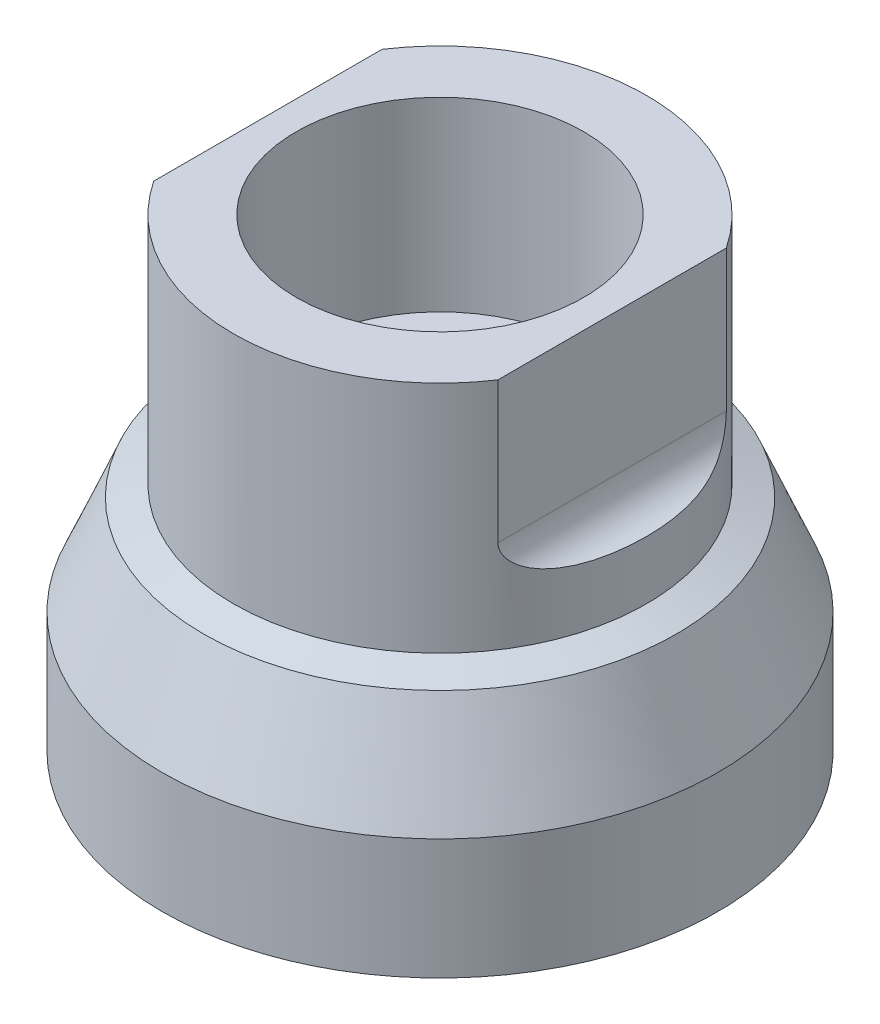
SolidWorks part; units mm, degrees
ref_plane "Front Plane" through (0, 0, 0) normal (0, 0, 1) x (1, 0, 0)
ref_plane "Top Plane" through (0, 0, 0) normal (0, 1, 0) x (1, 0, 0)
ref_plane "Right Plane" through (0, 0, 0) normal (1, 0, 0) x (0, 0, -1)
sketch "Sketch1" plane through (0, 0, 0) normal (1, 0, 0) x (0, 0, -1)
  line L0 (0, 0) -> (0, 17.2593) construction
  line L1 (0, 17.2593) -> (-15.24, 17.2593)
  line L2 (-15.24, 17.2593) -> (-15.24, 0)
  line L3 (-15.24, 0) -> (0, 0) construction
  line L4 (-15.24, 0) -> (-17.4625, -0.8089)
  line L5 (-17.4625, -0.8089) -> (-20.5105, -8.1407)
  line L6 (-20.5105, -17.0307) -> (-8.7845, -20.8407)
  line L7 (-8.7845, -20.8407) -> (0, -20.8407)
  line L8 (0, -20.8407) -> (0, 0) construction
  line L9 (-13.0457, 17.2593) -> (-13.0457, 0) construction
  line L10 (0, 17.2593) -> (0, -20.8407) construction
  line L11 (-20.5105, -8.1407) -> (-20.5105, -17.0307)
  line L12 (0, 17.2593) -> (0, -20.8407)
  dimension "D1" = 17.2593
  dimension "D2" = 38.1
  dimension "D3" = 110
  dimension "D4" = 41.021
  dimension "D5" = 38.1
  dimension "D6" = 30.48
  dimension "D7" = 25.4
  dimension "D8" = 34.29
  dimension "D9" = 18
  dimension "D10" = 34.925
revolve "Revolve1" add sketch "Sketch1" angle 360 mid plane about L12
sketch "Sketch3" plane through (0, 0, 0) normal (0, 0, 1) x (1, 0, 0)
  line L0 (-20.5105, -17.0307) -> (-8.7845, -20.8407) construction
  line L1 (-20.5105, -17.0307) -> (-5.161, -22.0181)
  line L2 (-12.8358, -19.5244) -> (-8.8848, -7.3647) construction
  point P7 (-8.7845, -20.8407)
  dimension "D1" = 3.81
ref_plane "Plane1" through (-5.872, 1.9079, 0) normal (0.9511, -0.309, 0) x (0, 0, -1)
sketch "Sketch4" plane through (-5.872, 1.9079, 0) normal (0.9511, -0.309, 0) x (0, 0, -1)
  line L0 (0, -25.0753) -> (0, -4.7553) construction
  line L1 (0, -7.7423) -> (0, -0.7693) construction
  line L2 (0, -4.7553) -> (-6.8326, -8.3882)
  line L3 (-6.8326, -8.3882) -> (-6.8326, -25.0753)
  line L4 (-6.8326, -25.0753) -> (0, -25.0753)
  line L5 (0, -25.0753) -> (0, -4.7553)
  dimension "D1" = 2.54
  dimension "D2" = 20.32
  dimension "D3" = 13.6652
  dimension "D4" = 118
revolve "Cut-Revolve2" cut sketch "Sketch4" angle 360 mid plane about L0
ref_plane "Plane2" through (-6.9638, -21.4323, 0) normal (-0.309, -0.9511, 0) x (0.9511, -0.309, 0)
ref_plane "Plane3" through (-7.3998, -22.7743, 0) normal (-0.309, -0.9511, 0) x (0.9511, -0.309, 0)
sketch "Sketch5" plane through (-7.3998, -22.7743, 0) normal (-0.309, -0.9511, 0) x (0.9511, -0.309, 0)
  circle A0 centre (-6.1742, 0) radius 6.858
  dimension "Outlet OD" = 13.716
curve "Helix/Spiral1"
sketch "Sketch8" plane through (0, 0, 0) normal (0, 0, 1) x (1, 0, 0)
  line L0 (0, -20.8407) -> (8.7845, -20.8407)
  line L1 (0, -17.0307) -> (0, -20.8407) construction
  line L2 (-7.6682, -20.8407) -> (8.7845, -20.8407) construction
  line L3 (8.7845, -20.8407) -> (20.5105, -17.0307) construction
  line L4 (8.7845, -20.8407) -> (20.5105, -17.0307)
  line L5 (20.5105, -17.0307) -> (20.5105, -33.1701)
  line L6 (20.5105, -33.1701) -> (0, -33.1701)
  line L7 (0, -33.1701) -> (0, -20.8407)
sketch "Sketch6" plane through (0, 0, 0) normal (0, 0, 1) x (1, 0, 0)
  line L0 (-12.8358, -19.5244) -> (-8.8848, -7.3647) construction
  line L4 (-6.2544, -21.7092) -> (-7.6347, -22.0025) construction
  line L5 (-7.6347, -22.0025) -> (-6.6904, -23.0512) construction
  line L6 (-6.6904, -23.0512) -> (-6.2544, -21.7092) construction
  line L7 (-7.4621, -21.9659) -> (-7.5166, -22.1336) construction
  line L8 (-6.4269, -21.7458) -> (-6.8085, -22.9201) construction
  line L9 (-7.6347, -22.0025) -> (-7.4894, -22.0497) construction
  line L10 (-6.6177, -22.333) -> (-6.4724, -22.3802) construction
  line L11 (-6.5451, -22.3566) -> (-6.7495, -22.9857) construction
  line L13 (-6.3407, -21.7275) -> (-7.4621, -21.9659)
  line L14 (-7.4621, -21.9659) -> (-7.5166, -22.1336)
  line L15 (-7.5166, -22.1336) -> (-6.6904, -23.0512)
  line L16 (-7.6347, -22.0025) -> (-8.6147, -21.6841) construction
  line L17 (-6.6904, -23.0512) -> (-6.5227, -23.1057) construction
  line L18 (-6.5227, -23.1057) -> (-6.4682, -22.938) construction
  line L19 (-6.4682, -22.938) -> (-6.4137, -22.7702) construction
  line L20 (-6.4137, -22.7702) -> (-6.3592, -22.6024) construction
  line L21 (-6.3592, -22.6024) -> (-6.3047, -22.4347) construction
  line L22 (-6.3047, -22.4347) -> (-6.2502, -22.2669) construction
  line L23 (-6.2502, -22.2669) -> (-6.1956, -22.0992) construction
  line L24 (-6.1956, -22.0992) -> (-6.1411, -21.9314) construction
  line L25 (-6.1411, -21.9314) -> (-6.0866, -21.7637) construction
  line L26 (-6.0866, -21.7637) -> (-6.2544, -21.7092) construction
  line L27 (-6.5451, -22.3566) -> (-6.3407, -21.7275) construction
  line L28 (-6.3407, -21.7275) -> (-6.6904, -23.0512)
  point P18 (-6.5099, -22.368)
  dimension "D1" = 1.4111
sweep "Sweep1" [suppressed] add profiles "Sketch6" path "Helix/Spiral1"
sketch "Sketch10" plane through (0, 0, 0) normal (0, 0, 1) x (1, 0, 0)
  line L0 (-12.8358, -19.5244) -> (-20.5105, -17.0307) construction
  line L1 (-20.5105, -17.0307) -> (-16.6639, -15.0708)
  line L2 (-16.6639, -15.0708) -> (-11.8924, -16.6211)
  line L3 (-12.8358, -19.5244) -> (-8.8848, -7.3647) construction
  line L4 (-11.8924, -16.6211) -> (-12.8358, -19.5244)
  line L6 (-20.5105, -17.0307) -> (-24.3571, -18.9906)
  line L7 (-24.3571, -18.9906) -> (-13.7791, -22.4276)
  line L8 (-13.7791, -22.4276) -> (-12.8358, -19.5244)
  point P4 (-18.5872, -16.0507)
  dimension "D1" = 45
  dimension "D2" = 3.8466
revolve "Cut-Revolve4" cut sketch "Sketch10" angle 360 mid plane about L8
pattern_circular "CirPattern1" count 3 over 360 about axis through (0, -0.8089, 0) along (0, 1, 0) of "Cut-Revolve2", "Sweep1", "Cut-Revolve4"
sketch "Sketch2" plane through (0, 0, 0) normal (0, 0, 1) x (1, 0, 0)
  line L0 (0, 17.2593) -> (0, -10.6807) construction
  line L1 (15.24, 17.2593) -> (-15.24, 17.2593) construction
  line L2 (0, -10.6807) -> (-7.8994, -6.4805)
  line L3 (-7.8994, -6.4805) -> (-7.8994, 17.2593)
  line L4 (-7.8994, 17.2593) -> (0, 17.2593)
  line L5 (0, 17.2593) -> (0, -10.6807)
  dimension "D1" = 118
  dimension "D2" = 27.94
  dimension "Schedule 40 ID" = 15.7988
revolve "Cut-Revolve1" cut sketch "Sketch2" angle 360 mid plane about L0
sketch "Sketch12" plane through (0, 17.2593, 0) normal (0, 1, 0) x (1, 0, 0)
  circle A0 centre (0, 0) radius 10.668
  dimension "D1" = 21.336
curve "Helix/Spiral2"
sketch "Sketch13" plane through (0, 17.2593, 0) normal (0, 1, 0) x (1, 0, 0)
  circle A0 centre (0, 0) radius 10.6045
  dimension "D1" = 21.209
extrude "Cut-Extrude1" cut sketch "Sketch13" against normal blind 13.716
sketch "Sketch19" plane through (0, 0, 0) normal (0, 0, 1) x (1, 0, 0)
  line L0 (-10.6045, 17.2593) -> (-10.6045, 3.5433) construction
  line L1 (10.6045, 3.5433) -> (10.6045, 17.2593) construction
  line L2 (-10.6045, 17.2593) -> (-10.6045, 3.5433)
  line L3 (10.6045, 3.5433) -> (10.6045, 17.2593)
  line L4 (10.6045, 3.5433) -> (-10.6045, 3.5433)
sketch "Sketch14" plane through (0, 0, 0) normal (1, 0, 0) x (0, 0, -1)
  line L0 (-10.7662, 17.2026) -> (-9.195, 18.1097) construction
  line L1 (-9.195, 18.1097) -> (-10.7662, 19.0169) construction
  line L2 (-10.7662, 19.0169) -> (-10.7662, 17.2026) construction
  line L3 (-9.3914, 17.9964) -> (-9.3914, 18.2231) construction
  line L4 (-10.5698, 17.316) -> (-10.5698, 18.9035) construction
  line L5 (-9.195, 18.1097) -> (-9.3914, 18.1097) construction
  line L6 (-10.5698, 18.1097) -> (-10.7662, 18.1097) construction
  line L7 (-10.668, 18.1097) -> (-10.668, 18.9602) construction
  line L8 (-10.668, 17.2593) -> (-9.3914, 17.9964)
  line L9 (-9.3914, 17.9964) -> (-9.3914, 18.2231)
  line L10 (-9.3914, 18.2231) -> (-10.7662, 19.0169)
  line L11 (-9.195, 18.1097) -> (-2.2184, 18.1097) construction
  line L12 (-10.7662, 19.0169) -> (-10.993, 19.0169) construction
  line L13 (-10.993, 19.0169) -> (-10.993, 18.7901) construction
  line L14 (-10.993, 18.7901) -> (-10.993, 18.5633) construction
  line L15 (-10.993, 18.5633) -> (-10.993, 18.3365) construction
  line L16 (-10.993, 18.3365) -> (-10.993, 18.1097) construction
  line L17 (-10.993, 18.1097) -> (-10.993, 17.883) construction
  line L18 (-10.993, 17.883) -> (-10.993, 17.6562) construction
  line L19 (-10.993, 17.6562) -> (-10.993, 17.4294) construction
  line L20 (-10.993, 17.4294) -> (-10.993, 17.2026) construction
  line L21 (-10.993, 17.2026) -> (-10.7662, 17.2026) construction
  line L22 (-10.668, 18.1097) -> (-10.668, 17.2593) construction
  line L23 (-10.668, 17.2593) -> (-10.7662, 19.0169)
  point P17 (-10.7155, 18.1097)
  dimension "Pitch Inlet" = 1.8143
sweep "Sweep2" [suppressed] add profiles "Sketch14" path "Helix/Spiral2"
sketch "Sketch15" plane through (0, 17.2593, 0) normal (0, 1, 0) x (1, 0, 0)
  circle A1 centre (0, 0) radius 15.24
  circle A2 centre (0, 0) radius 15.24
  dimension "D1" = 0
extrude "Cut-Extrude2" [suppressed] cut sketch "Sketch15" along normal blind 13.716
sketch "Sketch16" [suppressed] plane through (0, 17.2593, 0) normal (0, 1, 0) x (1, 0, 0)
  line L0 (2.0493, 10.3024) -> (0, 0) construction
  circle A0 centre (0, 0) radius 10.5042
  dimension "D1" = 1.143
extrude "Cut-Extrude3" [suppressed] cut sketch "Sketch16" against normal blind 13.716 draft 45
sketch "Sketch17" plane through (0, 0, 0) normal (0, 0, 1) x (1, 0, 0)
  line L0 (0, 0) -> (0, 17.2593) construction
  line L1 (-15.24, 17.2593) -> (-12.7, 17.2593)
  line L2 (-15.24, 17.2593) -> (-15.24, 4.3053)
  line L3 (-15.24, 4.3053) -> (-12.7, 4.3053)
  line L4 (-12.7, 17.2593) -> (-12.7, 4.3053)
  line L5 (15.24, 0) -> (-15.24, 0) construction
  line L6 (15.24, 17.2593) -> (-15.24, 17.2593) construction
  line L7 (12.7, 17.2593) -> (12.7, 4.3053)
  line L8 (15.24, 4.3053) -> (12.7, 4.3053)
  line L9 (15.24, 17.2593) -> (15.24, 4.3053)
  line L10 (15.24, 17.2593) -> (12.7, 17.2593)
  dimension "D1" = 25.4
  dimension "D2" = 12.954
extrude "Cut-Extrude4" cut sketch "Sketch17" against normal through all and the other way through all
fillet "Fillet1" radius 2.54 2 edges at (12.7, 4.3053, 0) (-12.7, 4.3053, 0)
sketch "Sketch20" plane through (0, 0, 0) normal (0, 1, 0) x (1, 0, 0)
  line L0 (-20.5105, 0) -> (20.5105, 0) construction
  line L1 (0, 20.5105) -> (0, -20.5105) construction
  circle A0 centre (0, 0) radius 20.5105 construction
  circle A1 centre (0, 0) radius 20.5105
sketch "Sketch21" [suppressed] plane through (0, -20.8407, 0) normal (0, -1, 0) x (1, 0, 0)
  line L0 (6.6317, 11.4865) -> (6.6317, -11.4865)
